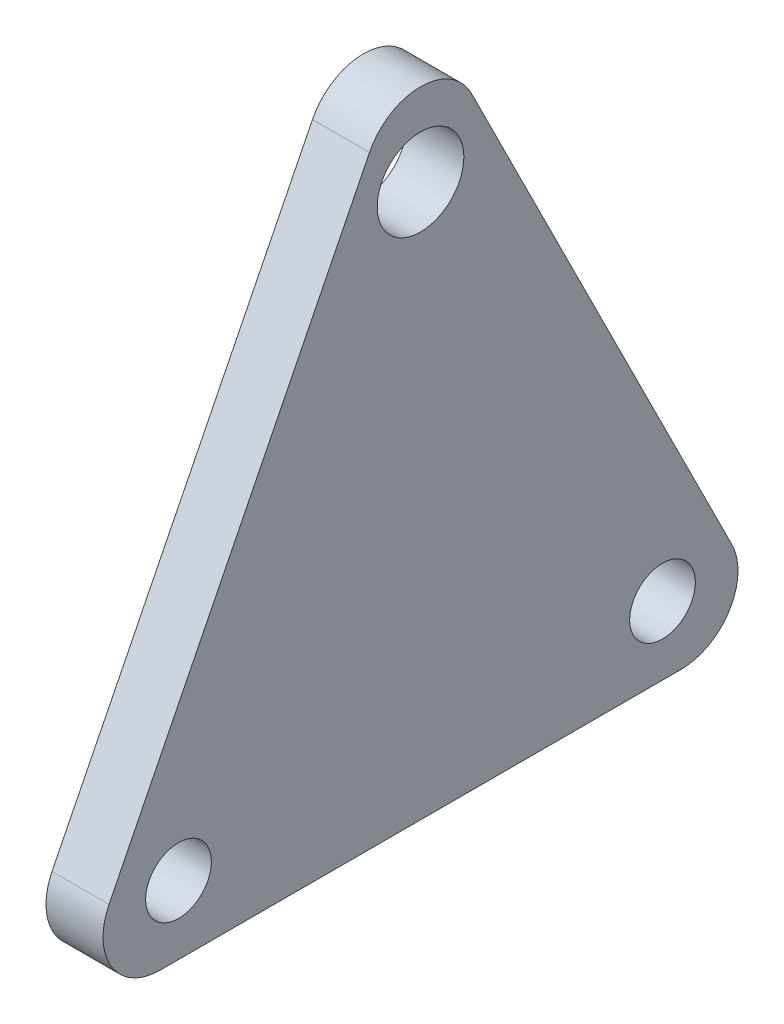
SolidWorks part; units mm, degrees
ref_plane "Front Plane" through (0, 0, 0) normal (0, 0, 1) x (1, 0, 0)
ref_plane "Top Plane" through (0, 0, 0) normal (0, 1, 0) x (1, 0, 0)
ref_plane "Right Plane" through (0, 0, 0) normal (1, 0, 0) x (0, 0, -1)
sketch "Sketch1" plane through (0, 0, 0) normal (1, 0, 0) x (0, 0, -1)
  line L0 (-13.4747, 0) -> (13.4747, 0) construction
  line L1 (0, 0) -> (0, 26.9494) construction
  line L2 (-13.4747, 0) -> (0, 26.9494) construction
  line L3 (0, 26.9494) -> (13.4747, 0) construction
  line L4 (13.4747, 0) -> (-13.4747, 0) construction
  line L5 (19.6394, -3.81) -> (-19.6394, -3.81)
  line L6 (-19.6394, -3.81) -> (0, 35.4688)
  line L7 (0, 35.4688) -> (19.6394, -3.81)
  circle A0 centre (-13.4747, 0) radius 1.8288
  circle A1 centre (0, 26.9494) radius 2.413
  circle A2 centre (13.4747, 0) radius 1.8288
  point P4 (0, 0)
  dimension "D3" = 3.6576
  dimension "D4" = 4.826
  dimension "D1" = 26.9494
  dimension "D2" = 3.81
extrude "Boss-Extrude1" add sketch "Sketch1" along normal blind 3.175
fillet "Fillet1" radius 3.175 3 edges at (1.5875, 35.4688, 0) (1.5875, -3.81, -19.6394) (1.5875, -3.81, 19.6394)
